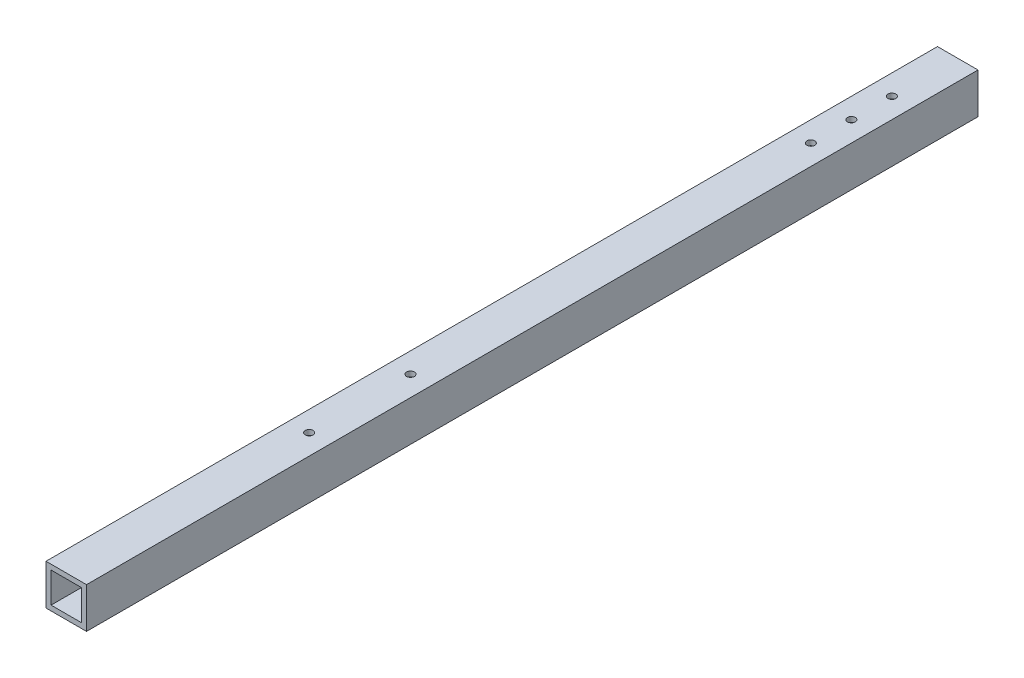
SolidWorks part; units mm, degrees
material "6061-T6 (SS)"
ref_plane "Front Plane" through (0, 0, 0) normal (0, 0, 1) x (1, 0, 0)
ref_plane "Top Plane" through (0, 0, 0) normal (0, 1, 0) x (1, 0, 0)
ref_plane "Right Plane" through (0, 0, 0) normal (1, 0, 0) x (0, 0, -1)
sketch "Sketch1" plane through (0, 0, 0) normal (0, 0, 1) x (1, 0, 0)
  line L0 (9.525, -9.525) -> (9.525, 9.525)
  line L1 (12.7, -12.7) -> (-12.7, -12.7)
  line L2 (12.7, -12.7) -> (12.7, 12.7)
  line L3 (12.7, 12.7) -> (-12.7, 12.7)
  line L4 (-12.7, -12.7) -> (-12.7, 12.7)
  line L5 (12.7, -12.7) -> (-12.7, 12.7) construction
  line L6 (12.7, 12.7) -> (-12.7, -12.7) construction
  line L7 (9.525, 9.525) -> (-9.525, 9.525)
  line L8 (-9.525, -9.525) -> (-9.525, 9.525)
  line L9 (9.525, -9.525) -> (-9.525, -9.525)
  point P0 (0, 0)
  dimension "D1" = 25.4
  dimension "D2" = 25.4
  dimension "D3" = 3.175
extrude "Boss-Extrude1" add sketch "Sketch1" along normal mid plane 558.8
sketch "Sketch2" plane through (0, 12.7, 0) normal (0, 1, 0) x (1, 0, 0)
  line L1 (12.7, 279.4) -> (-12.7, 279.4) construction
  point P0 (0, -63.627)
  point P1 (0, -216.027)
  point P3 (0, 187.325)
  point P4 (0, 279.4)
  dimension "D1" = 250.952
  dimension "D2" = 92.075
  dimension "D3" = 152.4
hole_wizard "#10 (0.1935) Diameter Hole1" positions "Sketch4" profile "Sketch3" hole size "#10" standard "ANSI Inch"
sketch "Sketch4" plane through (0, 12.7, 0) normal (0, 1, 0) x (1, 0, 0)
  point P0 (0, -63.627)
  point P3 (0, 187.325)
  point P12 (0, 212.725)
  point P13 (0, 238.125)
  dimension "D1" = 3
sketch "Sketch3" plane through (0, 12.7, 63.627) normal (1, 0, 0) x (0, 0, 1)
  line L0 (0, 0) -> (0, 52.2766)
  line L1 (0, 52.2766) -> (2.4574, 50.8)
  line L2 (2.4574, 50.8) -> (2.4574, 0)
  line L5 (2.4574, 0) -> (0, 0)
  line L10 (0, 52.2766) -> (-2.4575, 50.8) construction
  line L11 (0, -6.35) -> (0, 107.95) construction
  dimension "Hole Dia." = 4.9149
  dimension "Hole Depth" = 50.8
  dimension "Drill Angle" = 118
sketch "Sketch5" plane through (0, 12.7, 0) normal (0, 1, 0) x (1, 0, 0)
  circle A0 centre (0, -127.127) radius 2.4642
  circle A1 centre (0, -63.627) radius 2.4574 construction
  dimension "D1" = 63.5
extrude "Cut-Extrude1" cut sketch "Sketch5" against normal through all
